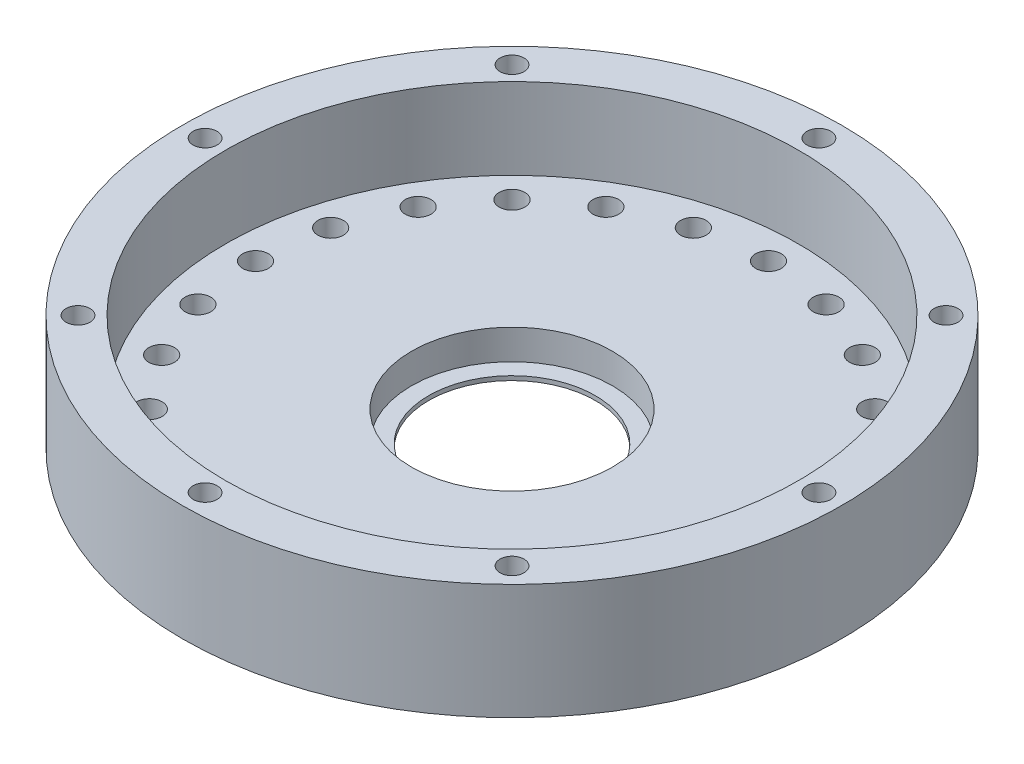
SolidWorks part; units mm, degrees
ref_plane "Front Plane" through (0, 0, 0) normal (0, 0, 1) x (1, 0, 0)
ref_plane "Top Plane" through (0, 0, 0) normal (0, 1, 0) x (1, 0, 0)
ref_plane "Right Plane" through (0, 0, 0) normal (1, 0, 0) x (0, 0, -1)
sketch "Sketch1" plane through (0, 0, 0) normal (0, 1, 0) x (1, 0, 0)
  circle A0 centre (0, 0) radius 77.1
  dimension "D1" = 154.2
extrude "Boss-Extrude1" add sketch "Sketch1" along normal blind 27
sketch "Sketch2" plane through (0, 27, 0) normal (0, 1, 0) x (1, 0, 0)
  circle A0 centre (0, 0) radius 67
  dimension "D1" = 134
extrude "Cut-Extrude1" cut sketch "Sketch2" against normal blind 19
sketch "Sketch3" plane through (0, 8, 0) normal (0, 1, 0) x (1, 0, 0)
  circle A1 centre (60, 0) radius 3
  circle A2 centre (57.9555, -15.5291) radius 3
  circle A3 centre (51.9615, -30) radius 3
  circle A4 centre (42.4264, -42.4264) radius 3
  circle A5 centre (30, -51.9615) radius 3
  circle A6 centre (15.5291, -57.9555) radius 3
  circle A7 centre (0, -60) radius 3
  circle A8 centre (-15.5291, -57.9555) radius 3
  circle A9 centre (-30, -51.9615) radius 3
  circle A10 centre (-42.4264, -42.4264) radius 3
  circle A11 centre (-51.9615, -30) radius 3
  circle A12 centre (-57.9555, -15.5291) radius 3
  circle A13 centre (-60, 0) radius 3
  circle A14 centre (-57.9555, 15.5291) radius 3
  circle A15 centre (-51.9615, 30) radius 3
  circle A16 centre (-42.4264, 42.4264) radius 3
  circle A17 centre (-30, 51.9615) radius 3
  circle A18 centre (-15.5291, 57.9555) radius 3
  circle A19 centre (0, 60) radius 3
  circle A20 centre (15.5291, 57.9555) radius 3
  circle A21 centre (30, 51.9615) radius 3
  circle A22 centre (42.4264, 42.4264) radius 3
  circle A27 centre (51.9615, 30) radius 3
  circle A28 centre (57.9555, 15.5291) radius 3
  point P13 (0, 0)
  dimension "D2" = 60
  dimension "D3" = 24
extrude "Cut-Extrude2" cut sketch "Sketch3" against normal blind 5
sketch "Sketch4" plane through (0, 0, 0) normal (0, -1, 0) x (1, 0, 0)
  circle A0 centre (0, 0) radius 23.5
  dimension "D1" = 47
extrude "Cut-Extrude3" cut sketch "Sketch4" along normal blind 7 from surface starting at face at (-15.5291, 8, 60.9555)
sketch "Sketch5" plane through (0, 8, 0) normal (0, 1, 0) x (1, 0, 0)
  circle A0 centre (0, 0) radius 19.5
  dimension "D1" = 39
extrude "Cut-Extrude4" cut sketch "Sketch5" against normal through all
sketch "Sketch6" plane through (0, 27, 0) normal (0, 1, 0) x (1, 0, 0)
  line L0 (0, 71.8) -> (0, 0) construction
  circle A0 centre (0, 71.8) radius 2.8
  circle A3 centre (50.7703, 50.7703) radius 2.8
  circle A4 centre (71.8, 0) radius 2.8
  circle A5 centre (50.7703, -50.7703) radius 2.8
  circle A6 centre (0, -71.8) radius 2.8
  circle A7 centre (-50.7703, -50.7703) radius 2.8
  circle A8 centre (-71.8, 0) radius 2.8
  circle A9 centre (-50.7703, 50.7703) radius 2.8
  point P19 (0, 0)
  dimension "D3" = 71.8
  dimension "D2" = 8
extrude "Cut-Extrude5" cut sketch "Sketch6" against normal blind 8
equation "\"N_pin\"= 24"
equation "\"R_pin\"= 60"
equation "\"d_pin\"= 13"
equation "\"e\"= 1.5"
equation "\"t_disk\"= 5"
equation "\"N_outpin\"= 8"
equation "\"R_outpin\"= 34"
equation "\"d_outpin\"= 13"
equation "\"N_lobes\"= \"N_pin\" - 1"
equation "\"d_outhole\"= \"d_outpin\" + 2 * \"e\""
equation "\"ratio\"= \"N_lobes\""
equation "\"d_center\"= 24"
equation "\"a_hole1\"= 0 / \"N_lobes\""
equation "\"a_hole2\"= 360 / \"N_disk\" / \"N_lobes\""
equation "\"a_hole3\"= 720 / \"N_disk\" / \"N_lobes\""
equation "\"N_disk\"= 3"
equation "\"t_gap\"= 1"
equation "\"L_stack\"= \"N_disk\" * \"t_disk\" + (\"N_disk\" - 1) * \"t_gap\""
equation "\"d_pinshaft\"= 6"
equation "\"d_ecc\"= 15"
equation "\"d_outbrg\"= 47"
equation "\"w_outbrg\"= 7"
equation "\"d_outshaft\"= 35"
equation "\"w_brg\"= 5"
equation "\"c_run\"= 0.5"
equation "\"c_ax\"= \"t_gap\""
equation "\"D_pocket\"= 2 * \"R_pin\" + \"d_pin\" + 2 * \"c_run\""
equation "\"h_pocket\"= \"L_stack\" + 2 * \"c_ax\""
equation "\"t_floor\"= 8"
equation "\"d_insert\"= 5.6"
equation "\"N_bolt\"= 8"
equation "\"R_bolt\"= \"D_pocket\" / 2 + 2 + \"d_insert\" / 2"
equation "\"D_housing\"= 2 * (\"R_bolt\" + \"d_insert\" / 2 + 2.5)"
equation "\"D1@Sketch1\"=\"D_housing\""
equation "\"D1@Boss-Extrude1\"=\"t_floor\"+\"h_pocket\""
equation "\"D1@Sketch2\"=\"D_pocket\""
equation "\"D1@Cut-Extrude1\"=\"h_pocket\""
equation "\"D1@Sketch3\"=\"d_pinshaft\""
equation "\"D2@Sketch3\"=\"R_pin\""
equation "\"D1@Cut-Extrude2\"=\"t_floor\"-3"
equation "\"D3@Sketch3\"=\"N_pin\""
equation "\"D1@Sketch4\"=\"d_outbrg\""
equation "\"D1@Cut-Extrude3\"=\"w_outbrg\""
equation "\"D1@Sketch5\"=\"d_outshaft\"+4"
equation "\"D1@Sketch6\"=\"d_insert\""
equation "\"D2@Sketch6\"=\"N_bolt\""
equation "\"D3@Sketch6\"=\"R_bolt\""
